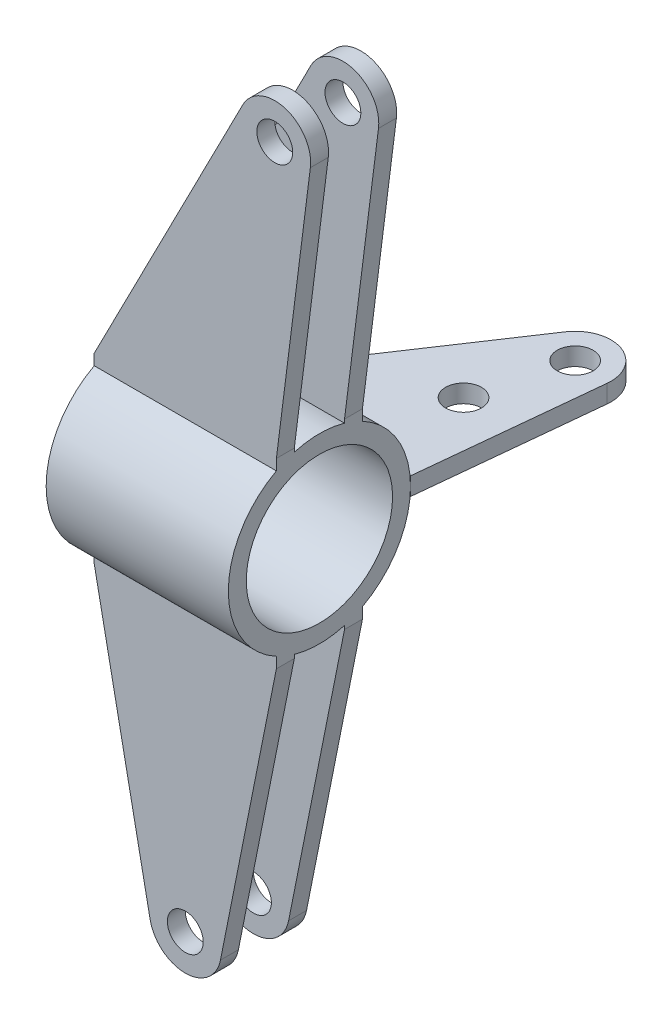
SolidWorks part; units mm, degrees
ref_plane "Front Plane" through (0, 0, 0) normal (0, 0, 1) x (1, 0, 0)
ref_plane "Top Plane" through (0, 0, 0) normal (0, 1, 0) x (1, 0, 0)
ref_plane "Right Plane" through (0, 0, 0) normal (1, 0, 0) x (0, 0, -1)
sketch "Sketch1" plane through (0, 0, 0) normal (0, 0, 1) x (1, 0, 0)
  line L0 (0, 101.6) -> (0, -101.6) construction
  line L1 (0, -101.6) -> (24.9498, 101.6) construction
  line L2 (0, 101.6) -> (24.9498, 101.6) construction
  line L3 (0, 0) -> (-95.758, 0) construction
  point P3 (0, 0)
  dimension "D1" = 203.2
  dimension "D2" = 7
  dimension "D3" = 95.758
sketch "Sketch2" plane through (0, 0, 0) normal (1, 0, 0) x (0, 0, -1)
  circle A0 centre (0, 0) radius 25.4
  circle A1 centre (0, 0) radius 20.4
  dimension "D1" = 50.8
  dimension "D2" = 5
extrude "Boss-Extrude1" add sketch "Sketch2" along normal mid plane 50.8
sketch "Sketch3" plane through (0, 0, 0) normal (0, 0, 1) x (1, 0, 0)
  line L0 (-25.4, 25.4) -> (16.0532, 106.1662)
  line L1 (-25.4, 25.4) -> (25.4, 25.4)
  line L2 (25.4, 25.4) -> (34.8709, 100.3463)
  line L3 (-25.4, -25.4) -> (-9.8067, -103.5566)
  line L4 (-25.4, -25.4) -> (25.4, -25.4)
  line L5 (25.4, -25.4) -> (9.8067, -103.5566)
  circle A0 centre (24.9498, 101.6) radius 5
  arc A1 (34.8709, 100.3463) -> (16.0532, 106.1662) centre (24.9498, 101.6) ccw
  circle A2 centre (0, -101.6) radius 5
  arc A3 (-9.8067, -103.5566) -> (9.8067, -103.5566) centre (0, -101.6) ccw
  dimension "D1" = 10
  dimension "D2" = 20
  dimension "D3" = 10
  dimension "D4" = 20
extrude "Boss-Extrude2" add sketch "Sketch3" along normal blind 5 from offset 7 separate body
extrude "Boss-Extrude3" add sketch "Sketch3<2>" against normal blind 5 from offset 7 separate body offset against normal yes
sketch "Sketch3<2>" plane through (0, 0, 0) normal (0, 0, 1) x (1, 0, 0) same geometry as "Sketch3"
sketch "Sketch4" plane through (0, 0, 0) normal (1, 0, 0) x (0, 0, -1)
  line L0 (-12, -25.4) -> (-7, -25.4) construction
  line L1 (12, -25.4) -> (7, -25.4) construction
  line L2 (12, 25.4) -> (7, 25.4) construction
  line L3 (-12, 25.4) -> (-7, 25.4) construction
  line L4 (-12, -25.4) -> (-7, -25.4)
  line L5 (12, -25.4) -> (7, -25.4)
  line L6 (12, 25.4) -> (7, 25.4)
  line L7 (-12, 25.4) -> (-7, 25.4)
  line L8 (-12, 25.4) -> (-12, 22.3866)
  line L9 (-7, 25.4) -> (-7, 24.4164)
  line L10 (7, 25.4) -> (7, 24.4164)
  line L11 (12, 25.4) -> (12, 22.3866)
  line L12 (-7, -25.4) -> (-7, -24.4164)
  line L13 (-12, -25.4) -> (-12, -22.3866)
  line L14 (7, -25.4) -> (7, -24.4164)
  line L15 (12, -25.4) -> (12, -22.3866)
  circle A0 centre (0, 0) radius 25.4 construction
  arc A1 (-12, -22.3866) -> (-7, -24.4164) centre (0, 0) ccw
  arc A2 (12, 22.3866) -> (7, 24.4164) centre (0, 0) ccw
  arc A3 (7, -24.4164) -> (12, -22.3866) centre (0, 0) ccw
  arc A4 (-7, 24.4164) -> (-12, 22.3866) centre (0, 0) ccw
extrude "Boss-Extrude4" add sketch "Sketch4" along normal mid plane 50.8
sketch "Sketch6" plane through (0, 0, 0) normal (0, 1, 0) x (1, 0, 0)
  line L0 (0, 0) -> (20.5175, 76.2) construction
  line L1 (0, 0) -> (24.9498, 0) construction
  line L2 (-25.4, 25.4) -> (12.1992, 81.7503)
  line L3 (30.4662, 75.1877) -> (25.4, 25.4)
  line L4 (-25.4, 25.4) -> (25.4, 25.4)
  circle A0 centre (20.5175, 76.2) radius 5
  arc A1 (30.4662, 75.1877) -> (12.1992, 81.7503) centre (20.5175, 76.2) ccw
  circle A2 centre (13.9136, 51.6735) radius 5
  dimension "D3" = 10
  dimension "D4" = 20
  dimension "D1" = 74.93
  dimension "D2" = 76.2
  dimension "D5" = 25.4
extrude "Boss-Extrude6" add sketch "Sketch6" along normal mid plane 5 separate body
